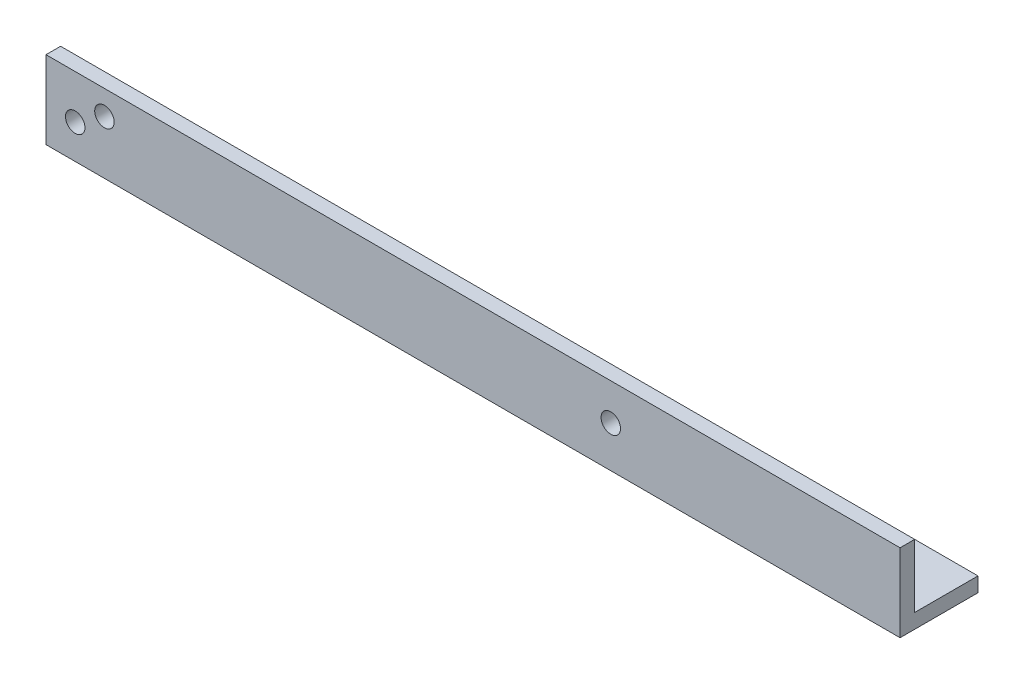
SolidWorks part; units mm, degrees
material "6061 Alloy"
ref_plane "Front Plane" through (0, 0, 0) normal (0, 0, 1) x (1, 0, 0)
ref_plane "Top Plane" through (0, 0, 0) normal (0, 1, 0) x (1, 0, 0)
ref_plane "Right Plane" through (0, 0, 0) normal (1, 0, 0) x (0, 0, -1)
sketch "Sketch1" plane through (0, 0, 0) normal (1, 0, 0) x (0, 0, -1)
  line L0 (0, 0) -> (0, -25.4)
  line L1 (0, -25.4) -> (25.4, -25.4)
  line L2 (25.4, -25.4) -> (25.4, -20.6375)
  line L3 (25.4, -20.6375) -> (4.7625, -20.6375)
  line L4 (4.7625, -20.6375) -> (4.7625, 0)
  line L5 (4.7625, 0) -> (0, 0)
  dimension "D1" = 4.7625
  dimension "D2" = 4.7625
  dimension "D3" = 25.4
  dimension "D4" = 25.4
extrude "Boss-Extrude1" add sketch "Sketch1" along normal blind 278.384
sketch "Sketch3" plane through (0, 0, -4.7625) normal (0, 0, -1) x (-1, 0, 0)
  line L0 (0, -20.6375) -> (0, 0) construction
  line L1 (-278.384, -25.4) -> (0, -25.4) construction
  circle A0 centre (-9.525, -14.2875) radius 3.175
  circle A1 centre (-19.05, -7.9375) radius 3.175
  dimension "D1" = 6.35
  dimension "D2" = 6.35
  dimension "D3" = 9.525
  dimension "D4" = 19.05
  dimension "D5" = 11.1125
  dimension "D6" = 17.4625
extrude "Cut-Extrude1" cut sketch "Sketch3" against normal up to next
sketch "Sketch4" plane through (0, 0, 0) normal (0, 0, 1) x (1, 0, 0)
  circle A0 centre (184.0953, -11.9296) radius 3.175 construction
  circle A1 centre (184.0953, -11.9296) radius 3.175
extrude "Cut-Extrude2" cut sketch "Sketch4" against normal up to next
sketch "Sketch5" plane through (0, -25.4, 0) normal (0, -1, 0) x (1, 0, 0)
  circle A0 centre (240.284, -12.7) radius 3.175 construction
  circle A1 centre (265.684, -12.7) radius 3.175 construction
  circle A2 centre (240.284, -12.7) radius 3.175
  circle A3 centre (265.684, -12.7) radius 3.175
extrude "Cut-Extrude4" cut sketch "Sketch5" against normal up to next
